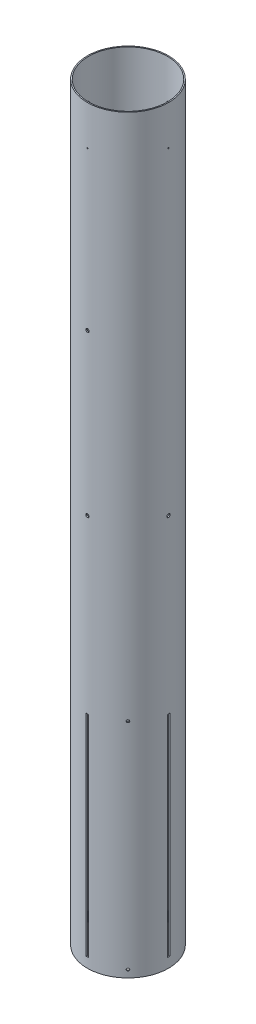
SolidWorks part; units mm, degrees
material "C-Glass Fiber"
ref_plane "Front Plane" through (0, 0, 0) normal (0, 0, 1) x (1, 0, 0)
ref_plane "Top Plane" through (0, 0, 0) normal (0, 1, 0) x (1, 0, 0)
ref_plane "Right Plane" through (0, 0, 0) normal (1, 0, 0) x (0, 0, -1)
sketch "Sustainer Tube Profile" plane through (0, 0, 0) normal (0, 1, 0) x (1, 0, 0)
  circle A0 centre (0, 0) radius 76.2
  circle A1 centre (0, 0) radius 78.359
  dimension "D2" = 156.718
extrude "Sustainer Tube Body" add sketch "Sustainer Tube Profile" along normal blind 1447.8
ref_plane "Plane1" through (0, 0, 78.359) normal (0, 0, 1) x (1, 0, 0)
sketch "Fin Slot Profile" plane through (0, 0, 78.359) normal (0, 0, 1) x (1, 0, 0)
  line L0 (0, 0) -> (0, 1447.8) construction
  line L5 (76.2, 1447.8) -> (-76.2, 1447.8) construction
  line L6 (-78.359, 0) -> (78.359, 0) construction
  line L7 (2.3813, 19.05) -> (-2.3813, 19.05)
  line L8 (0, 19.05) -> (0, 425.45)
  line L9 (2.3813, 425.45) -> (-2.3813, 425.45)
  line L10 (-2.3813, 19.05) -> (-2.3813, 425.45)
  line L11 (2.3813, 19.05) -> (2.3813, 425.45)
  dimension "D1" = 406.4
  dimension "D2" = 19.05
  dimension "D3" = 2.3813
extrude "Fin Slot Cut" cut sketch "Fin Slot Profile" against normal up to surface (2.1962 mm away) contours L7 L11 L9 L8 | L10 L7 L8 L9 region at (1.1906, 222.25, 78.359) region at (-1.1906, 222.25, 78.359) up to face at (0, 1447.8, 76.2)
pattern_circular "Fin Slot Pattern" count 4 over 360 about axis through (0, 1447.8, 0) along (0, 1, 0) of "Fin Slot Cut"
sketch "Sketch1" plane through (0, 0, 0) normal (0, 0, 1) x (1, 0, 0)
  line L0 (76.2, 1447.8) -> (-76.2, 1447.8) construction
  circle A0 centre (0, 1371.6) radius 1.143
  dimension "D1" = 2.286
  dimension "D2" = 76.2
extrude "Cut-Extrude1" cut sketch "Sketch1" against normal through all both and the other way through all
pattern_circular "CirPattern1" count 4 over 360 about axis through (0, 1447.8, 0) along (0, 1, 0) of "Cut-Extrude1"
sketch "Sketch2" plane through (0, 0, 0) normal (0, 0, 1) x (1, 0, 0)
  line L0 (76.2, 1447.8) -> (-76.2, 1447.8) construction
  circle A0 centre (0, 1066.8) radius 3.175
  dimension "D1" = 6.35
  dimension "D2" = 381
extrude "Cut-Extrude2" cut sketch "Sketch2" against normal through all both and the other way through all
sketch "Sketch3" plane through (0, 0, 0) normal (0, 0, 1) x (1, 0, 0)
  line L0 (78.359, 1447.8) -> (-78.359, 1447.8) construction
  circle A0 centre (0, 756.9962) radius 3.175
  dimension "D2" = 6.35
  dimension "D1" = 690.8038
extrude "Cut-Extrude3" cut sketch "Sketch3" against normal through all both and the other way through all
pattern_circular "CirPattern2" count 4 over 360 about axis through (0, 1447.8, 0) along (0, 1, 0) of "Cut-Extrude3"
ref_plane "Plane2" through (55.4082, 0, 55.4082) normal (0.7071, 0, 0.7071) x (0, -1, 0)
sketch "Sketch4" plane through (55.4082, 0, 55.4082) normal (0.7071, 0, 0.7071) x (0, -1, 0)
  circle A0 centre (-14.0462, 0) radius 2.5019
  circle A1 centre (-429.4429, 0) radius 2.5019
  dimension "D2" = 14.0462
  dimension "D3" = 429.4429
extrude "Cut-Extrude4" cut sketch "Sketch4" against normal up to surface and the other way through all up to face at (-76.1373, 756.269, 3.0906)
equation "\"Length\"= 57"
equation "\"Outer Diameter\"= 6.17"
equation "\"Inner Diameter\"= 6"
equation "\"Wall Thickness\"= 0.085"
equation "\"D1@Sustainer Tube Profile\" = \"Inner Diameter\""
equation "\"D2@Sustainer Tube Profile\" = \"Outer Diameter\""
equation "\"D1@Sustainer Tube Body\" = \"Length\""
equation "\"Root Chord\"= 16"
equation "\"Fin Offset\"= 3 / 4"
equation "\"D1@Fin Slot Profile\"=\"Root Chord\" "
equation "\"D2@Fin Slot Profile\" = \"Fin Offset\""
equation "\"Fin Thickness\"= ( 3 / 16 ) / 2"
equation "\"D3@Fin Slot Profile\"=\"Fin Thickness\""
equation "\"Shear Pin Dia\"= 3 / 32"
equation "\"Shear Pin Offset\"= 3"
equation "\"Bulkhead Screw Dia\"= 1 / 4"
equation "\"Bulkhead Screw Offset\"= 24.197 + 3"
equation "\"Rail Button Dia\"= 0.197"
equation "\"Rail Button Aft Offset\"= 0.553"
equation "\"Rail Button Forward Offset\"= 16.9072"
equation "\"Vent Hole Dia\"= 1 / 4"
equation "\"Vent Hole Offset\"= 15"
equation "\"D1@Sketch2\"=\"Vent Hole Dia\""
equation "\"D2@Sketch2\"=\"Vent Hole Offset\""
equation "\"D1@Sketch3\"=\"Bulkhead Screw Offset\""
equation "\"D2@Sketch3\"=\"Bulkhead Screw Dia\""
equation "\"D1@Sketch4\"=\"Rail Button Dia\""
equation "\"D2@Sketch4\"=\"Rail Button Aft Offset\""
equation "\"D3@Sketch4\"=\"Rail Button Forward Offset\""
